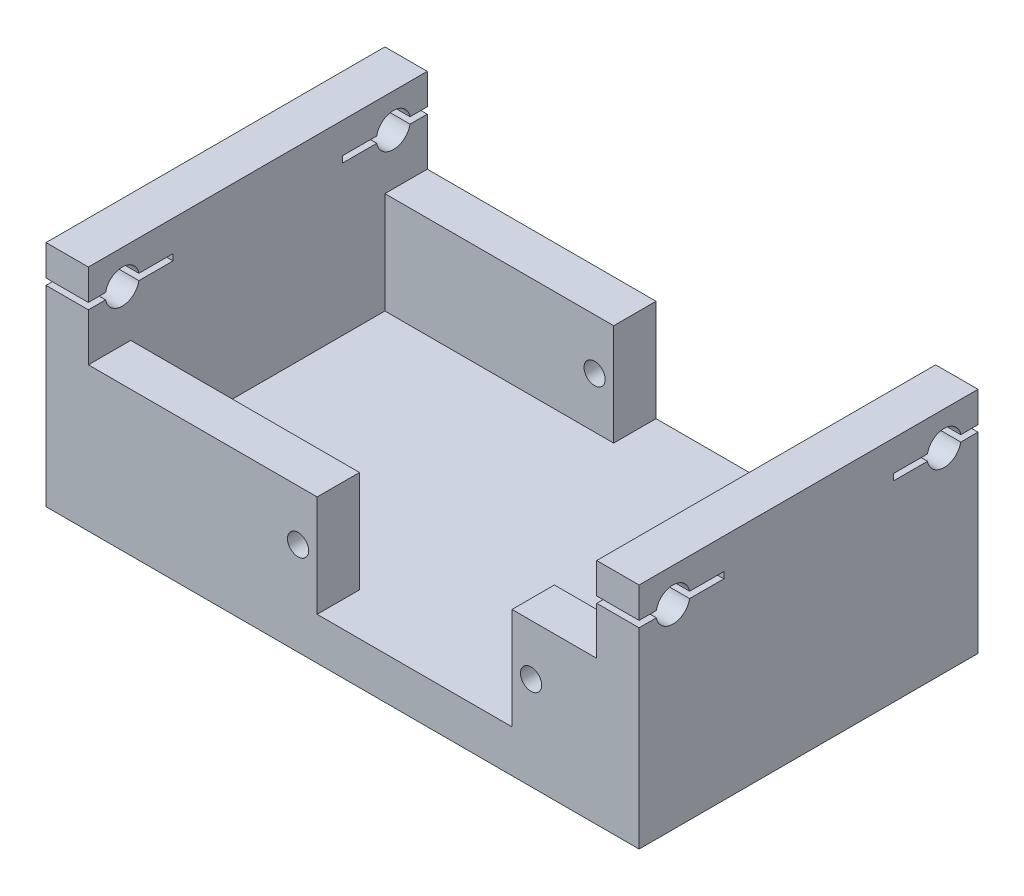
SolidWorks part; units mm, degrees
ref_plane "Front Plane" through (0, 0, 0) normal (0, 0, 1) x (1, 0, 0)
ref_plane "Top Plane" through (0, 0, 0) normal (0, 1, 0) x (1, 0, 0)
ref_plane "Right Plane" through (0, 0, 0) normal (1, 0, 0) x (0, 0, -1)
sketch "Sketch1" plane through (0, 0, 0) normal (0, 1, 0) x (1, 0, 0)
  line L1 (-35, -20) -> (35, -20)
  line L2 (-35, -20) -> (-35, 20)
  line L3 (-35, 20) -> (35, 20)
  line L4 (35, -20) -> (35, 20)
  line L5 (-35, -20) -> (35, 20) construction
  line L6 (-35, 20) -> (35, -20) construction
  point P0 (0, 0)
  dimension "D1" = 70
  dimension "D2" = 40
extrude "Boss-Extrude1" add sketch "Sketch1" along normal blind 5
sketch "Sketch2" plane through (0, 5, 0) normal (0, 1, 0) x (1, 0, 0)
  line L0 (-3, -20) -> (-3, -15)
  line L1 (-35, -20) -> (35, -20) construction
  line L2 (-3, -15) -> (-30, -15)
  line L3 (-35, 20) -> (-35, -20) construction
  line L4 (-30, -15) -> (-30, 15)
  line L6 (-30, 15) -> (-3, 15)
  line L7 (-3, 15) -> (-3, 20)
  line L8 (35, 20) -> (-35, 20) construction
  line L9 (-3, 20) -> (-35, 20)
  line L10 (-35, 20) -> (-35, -20)
  line L11 (-35, -20) -> (-3, -20)
  line L12 (20, -15) -> (30, -15)
  line L13 (35, -20) -> (35, 20) construction
  line L14 (30, -15) -> (30, 15)
  line L15 (30, 15) -> (20, 15)
  line L16 (20, 15) -> (20, 20)
  line L17 (20, 20) -> (35, 20)
  line L18 (35, 20) -> (35, -20)
  line L19 (35, -20) -> (20, -20)
  line L20 (20, -20) -> (20, -15)
  dimension "D1" = 32
  dimension "D2" = 5
  dimension "D3" = 30
  dimension "D4" = 5
  dimension "D5" = 5
  dimension "D6" = 15
  dimension "D9" = 5
extrude "Boss-Extrude2" add sketch "Sketch2" along normal blind 12
sketch "Sketch3" plane through (0, 17, 0) normal (0, 1, 0) x (1, 0, 0)
  line L0 (35, 20) -> (20, 20) construction
  line L1 (35, -20) -> (30, -20)
  line L2 (35, -20) -> (35, 20)
  line L3 (35, 20) -> (30, 20)
  line L4 (30, -20) -> (30, 20)
  line L5 (30, 15) -> (30, -15) construction
  line L6 (-35, -20) -> (-3, -20) construction
  line L7 (-35, 20) -> (-30, 20)
  line L8 (-35, 20) -> (-35, -20)
  line L9 (-35, -20) -> (-30, -20)
  line L10 (-30, 20) -> (-30, -20)
  line L11 (-30, -15) -> (-30, 15) construction
extrude "Boss-Extrude3" add sketch "Sketch3" along normal blind 10
sketch "Sketch5" plane through (-35, 0, 0) normal (-1, 0, 0) x (0, 0, 1)
  line L0 (-20, 27) -> (20, 27) construction
  line L1 (20, 27) -> (20, 0) construction
  line L2 (0, -2.75) -> (0, 2.75) construction
  circle A0 centre (16, 23) radius 2
  circle A1 centre (-16, 23) radius 2
  dimension "D1" = 4
  dimension "D2" = 4
  dimension "D3" = 4
extrude "Cut-Extrude1" cut sketch "Sketch5" against normal through all
sketch "Sketch7" plane through (0, 0, 15) normal (0, 0, -1) x (-1, 0, 0)
  line L0 (-20, 17) -> (-20, 5) construction
  line L1 (3, 17) -> (3, 5) construction
  line L2 (3, 17) -> (30, 17) construction
  line L3 (-30, 17) -> (-20, 17) construction
  circle A0 centre (-22.25, 11) radius 1.25
  circle A1 centre (5.25, 11) radius 1.25
  dimension "D1" = 2.5
  dimension "D2" = 2.25
  dimension "D4" = 6
  dimension "D5" = 2.5
  dimension "D6" = 6
  dimension "D3" = 2.25
extrude "Cut-Extrude3" cut sketch "Sketch7" against normal through all and the other way through all
sketch "Sketch8" plane through (-35, 0, 0) normal (-1, 0, 0) x (0, 0, 1)
  line L0 (20, 27) -> (20, 0) construction
  line L1 (20, 23.375) -> (10, 23.375)
  line L2 (20, 23.375) -> (20, 22.625)
  line L3 (20, 22.625) -> (10, 22.625)
  line L4 (-20, 23.375) -> (-20, 22.625)
  line L5 (-20, 27) -> (-20, 0) construction
  line L6 (10, 23.375) -> (10, 22.625)
  line L7 (-10, 23.375) -> (-10, 22.625)
  line L8 (-10, 23.375) -> (-20, 23.375)
  line L9 (-10, 22.625) -> (-20, 22.625)
  circle A0 centre (16, 23) radius 2 construction
  dimension "D1" = 0.75
  dimension "D2" = 0.375
  dimension "D3" = 10
  dimension "D4" = 10
extrude "Cut-Extrude4" cut sketch "Sketch8" against normal through all
